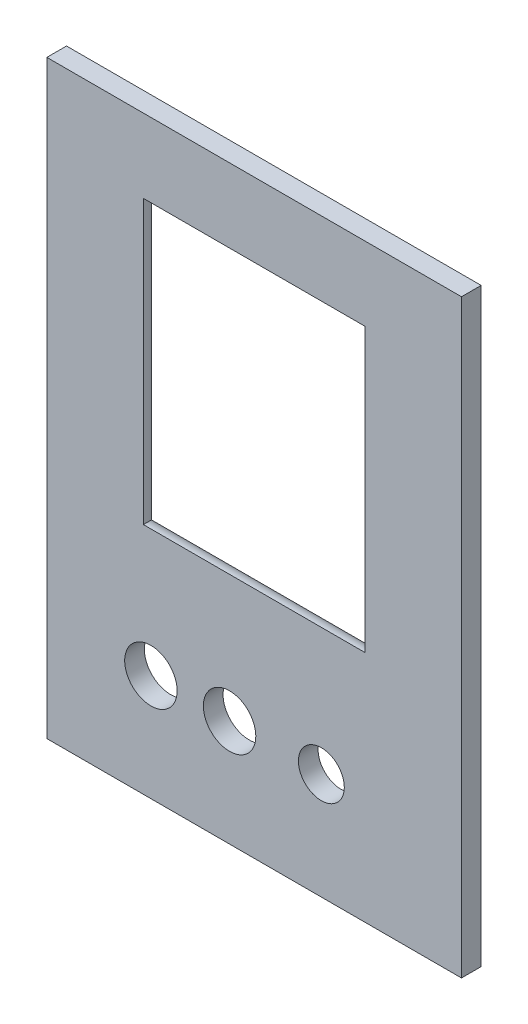
SolidWorks part; units mm, degrees
ref_plane "Спереди" through (0, 0, 0) normal (0, 0, 1) x (1, 0, 0)
ref_plane "Сверху" through (0, 0, 0) normal (0, 1, 0) x (1, 0, 0)
ref_plane "Справа" through (0, 0, 0) normal (1, 0, 0) x (0, 0, -1)
ref_plane "Плоскость1" through (0, -44.4555, -16.1805) normal (0, -0.9397, -0.342) x (-1, 0, 0)
sketch "Эскиз1" plane through (0, 0, 0) normal (0, 0, 1) x (1, 0, 0)
  line L1 (31.625, -48.0063) -> (-31.625, -48.0063)
  line L2 (31.625, -48.0063) -> (31.625, 41.9937)
  line L3 (31.625, 41.9937) -> (-31.625, 41.9937)
  line L4 (-31.625, -48.0063) -> (-31.625, 41.9937)
  line L5 (31.625, -48.0063) -> (-31.625, 41.9937) construction
  line L6 (31.625, 41.9937) -> (-31.625, -48.0063) construction
  line L8 (-31.625, 46.6633) -> (-31.625, -65.1601) construction
  point P0 (0, -3.0063)
  dimension "D1" = 90
extrude "Бобышка-Вытянуть1" add sketch "Эскиз1" along normal blind 3
sketch "Эскиз2" plane through (0, 0, 0) normal (0, 0, 1) x (1, 0, 0)
  line L16 (16.9, -12.3685) -> (16.9, 30.7315)
  line L17 (-16.9, -12.3685) -> (16.9, -12.3685)
  line L18 (-16.9, 30.7315) -> (-16.9, -12.3685)
  line L19 (16.9, 30.7315) -> (-16.9, 30.7315)
  line L20 (16.9, -12.3685) -> (16.9, 30.7315)
  line L21 (-16.9, -12.3685) -> (16.9, -12.3685)
  line L22 (-16.9, 30.7315) -> (-16.9, -12.3685)
  line L23 (16.9, 30.7315) -> (-16.9, 30.7315)
  circle A2 centre (10.25, -31.7685) radius 3.5
  circle A3 centre (10.25, -31.7685) radius 3.5
  circle A4 centre (-3.75, -31.7535) radius 4
  circle A5 centre (-15.75, -31.7535) radius 4
  dimension "D3" = 8
  dimension "D1" = 0
  dimension "D2" = 0.5
extrude "Вырез-Вытянуть1" cut sketch "Эскиз2" along normal through all
fillet "Скругление1" radius 3 4 edges at (0, -12.3685, 0) (16.9, 9.1815, 0) (0, 30.7315, 0) (-16.9, 9.1815, 0)
